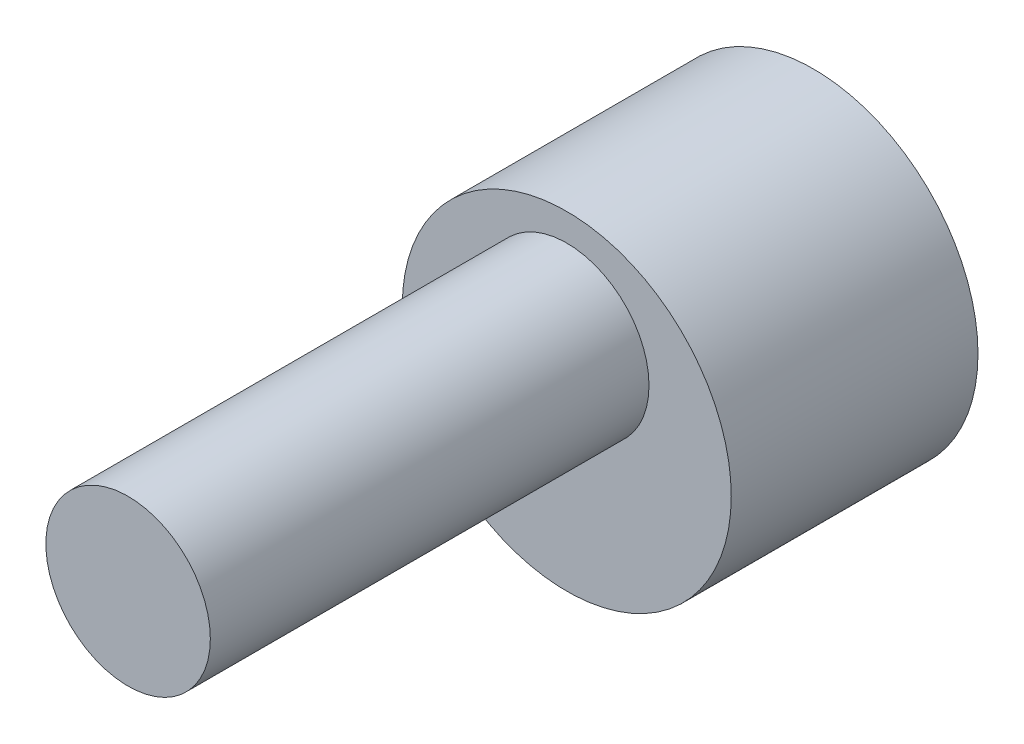
SolidWorks part; units mm, degrees
ref_plane "Front" through (0, 0, 0) normal (0, 0, 1) x (1, 0, 0)
ref_plane "Top" through (0, 0, 0) normal (0, 1, 0) x (1, 0, 0)
ref_plane "Right" through (0, 0, 0) normal (1, 0, 0) x (0, 0, -1)
sketch "Esquisse1" plane through (0, 0, 0) normal (0, 0, 1) x (1, 0, 0)
  circle A0 centre (0, 0) radius 6
  dimension "D1" = 12
extrude "Boss.-Extru.1" add sketch "Esquisse1" along normal blind 9
sketch "Esquisse2" plane through (0, 0, 9) normal (0, 0, 1) x (1, 0, 0)
  line L0 (0, 0) -> (0, 2) construction
  circle A0 centre (0, 2) radius 3
  dimension "D1" = 6
  dimension "D2" = 2
extrude "Boss.-Extru.2" add sketch "Esquisse2" along normal blind 16
